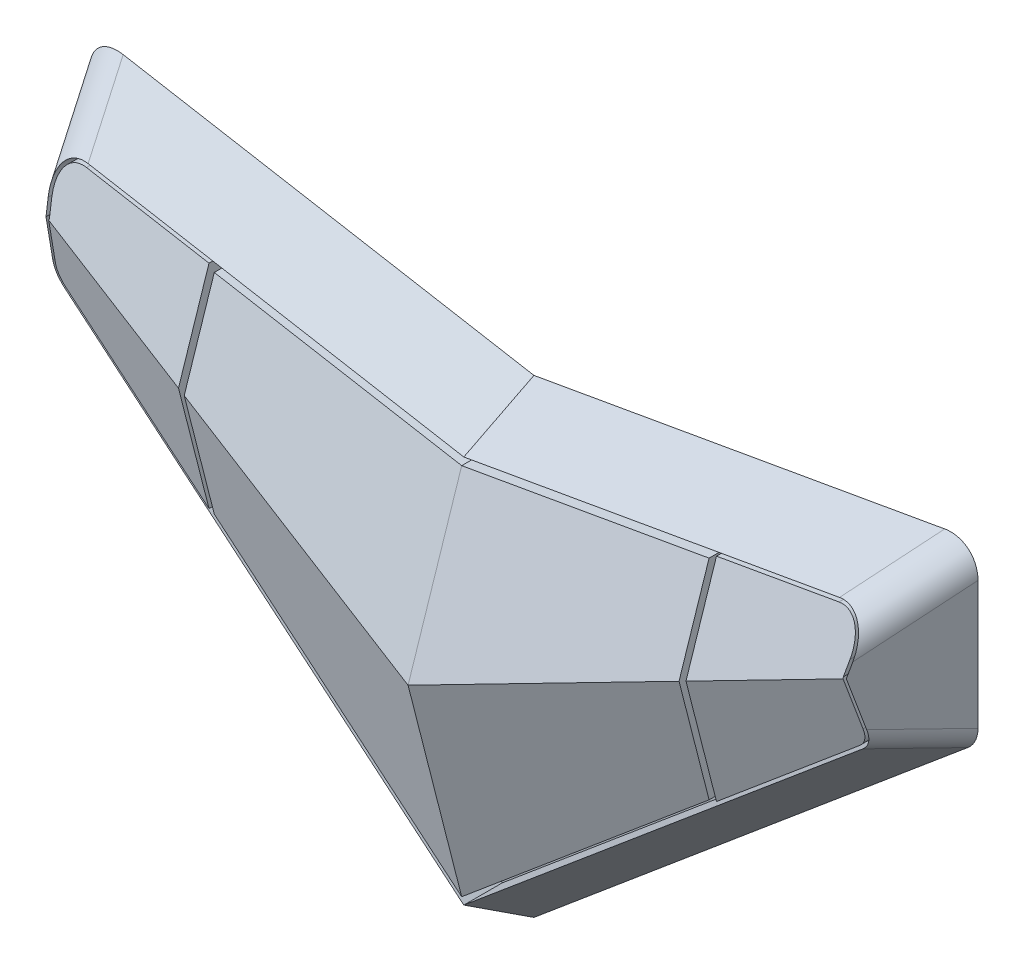
SolidWorks part; units mm, degrees
ref_plane "前视基准面" through (0, 0, 0) normal (0, 0, 1) x (1, 0, 0)
ref_plane "上视基准面" through (0, 0, 0) normal (0, 1, 0) x (1, 0, 0)
ref_plane "右视基准面" through (0, 0, 0) normal (1, 0, 0) x (0, 0, -1)
other "Configuration Table"
sketch "草图1" plane through (0, 0, 0) normal (0, 0, 1) x (1, 0, 0)
  line L0 (0, 79.8108) -> (0, -65.0792) construction
  line L1 (0, 74) -> (70, 86.3429)
  line L2 (70, 86.3429) -> (70, 58.737)
  line L3 (70, 58.737) -> (0, 0)
  line L4 (-70, 58.737) -> (0, 0)
  line L5 (-70, 86.3429) -> (-70, 58.737)
  line L6 (0, 74) -> (-70, 86.3429)
  point P5 (71.2745, 57.3374)
  point P8 (60, 66.0101)
  point P11 (70, 70)
  point P12 (70, 57.483)
  dimension "D1" = 70
  dimension "D2" = 130
  dimension "D3" = 74
  dimension "D4" = 100
ref_plane "基准面1" through (0, 0, 20) normal (0, 0, 1) x (1, 0, 0)
sketch "草图2" plane through (0, 0, 20) normal (0, 0, 1) x (1, 0, 0)
  line L12 (60, 74.4254) -> (0, 63.8457)
  line L13 (60, 63.4001) -> (60, 74.4254)
  line L14 (0, 13.0541) -> (60, 63.4001)
  line L15 (-60, 63.4001) -> (0, 13.0541)
  line L16 (-60, 74.4254) -> (-60, 63.4001)
  line L17 (0, 63.8457) -> (-60, 74.4254)
  line L18 (60, 74.4254) -> (0, 63.8457)
  line L19 (60, 63.4001) -> (60, 74.4254)
  line L20 (0, 13.0541) -> (60, 63.4001)
  line L21 (-60, 63.4001) -> (0, 13.0541)
  line L22 (-60, 74.4254) -> (-60, 63.4001)
  line L23 (0, 63.8457) -> (-60, 74.4254)
  dimension "D1" = 10
loft "放样1" add profiles "草图1", "草图2"
chamfer "倒角1" distance 10 angle 45 4 edges
fillet "圆角3" radius 5 4 edges
sketch "草图7" plane through (0, 0, 0) normal (0, 0, 1) x (1, 0, 0)
  line L0 (-40, 75.4399) -> (-40, 40.7801)
  line L1 (-59.2234, 78.8295) -> (0, 68.3869) construction
  line L2 (0, 7.2161) -> (-62.8746, 59.9742) construction
  line L3 (-40, 40.7801) -> (0, 7.2161)
  line L4 (0, 7.2161) -> (0, 41.623) construction
  line L5 (-40, 75.4399) -> (0, 68.3869)
  line L6 (40, 75.4399) -> (0, 68.3869)
  line L7 (40, 40.7801) -> (0, 7.2161)
  line L8 (40, 75.4399) -> (40, 40.7801)
  line L9 (-39, 74.2482) -> (0, 67.3714)
  line L10 (39, 74.2482) -> (0, 67.3714)
  line L11 (39, 74.2482) -> (39, 41.2464)
  line L12 (39, 41.2464) -> (0, 8.5215)
  line L13 (-39, 41.2464) -> (0, 8.5215)
  line L14 (-39, 74.2482) -> (-39, 41.2464)
  dimension "D1" = 40
  dimension "D2" = 1
extrude "切除-拉伸2" cut sketch "草图7" along normal through all from offset 5
sketch "草图9" plane through (0, 0, 0) normal (0, 0, 1) x (1, 0, 0)
  line L0 (-40, 75.4399) -> (0, 68.3869) construction
  line L1 (40, 75.4399) -> (0, 68.3869) construction
  line L2 (40, 75.4399) -> (59.2234, 78.8295) construction
  line L3 (63.4224, 73.1743) -> (63.0817, 71.0385) construction
  line L4 (63.0817, 71.0385) -> (64.1526, 63.549) construction
  line L5 (62.8746, 59.9742) -> (40, 40.7801) construction
  line L6 (0, 7.2161) -> (40, 40.7801) construction
  line L7 (-40, 40.7801) -> (0, 7.2161) construction
  line L8 (-40, 40.7801) -> (-62.8746, 59.9742) construction
  line L9 (-64.1526, 63.549) -> (-63.0817, 71.0385) construction
  line L10 (-63.0817, 71.0385) -> (-63.4224, 73.1743) construction
  line L11 (-59.2234, 78.8295) -> (-40, 75.4399) construction
  line L12 (-40, 75.4399) -> (0, 68.3869)
  line L13 (40, 75.4399) -> (0, 68.3869)
  line L14 (40, 75.4399) -> (59.2234, 78.8295)
  line L15 (63.4224, 73.1743) -> (63.0817, 71.0385)
  line L16 (63.0817, 71.0385) -> (64.1526, 63.549)
  line L17 (62.8746, 59.9742) -> (40, 40.7801)
  line L18 (0, 7.2161) -> (40, 40.7801)
  line L19 (-40, 40.7801) -> (0, 7.2161)
  line L20 (-40, 40.7801) -> (-62.8746, 59.9742)
  line L21 (-64.1526, 63.549) -> (-63.0817, 71.0385)
  line L22 (-63.0817, 71.0385) -> (-63.4224, 73.1743)
  line L23 (-59.2234, 78.8295) -> (-40, 75.4399)
  line L24 (-59.3102, 78.3371) -> (-40.0868, 74.9475)
  line L25 (-40.0868, 74.9475) -> (0, 67.8791)
  line L26 (40.0868, 74.9475) -> (0, 67.8791)
  line L27 (40.0868, 74.9475) -> (59.3102, 78.3371)
  line L28 (62.9286, 73.2531) -> (62.576, 71.0426)
  line L29 (62.576, 71.0426) -> (63.6577, 63.4783)
  line L30 (62.5532, 60.3572) -> (39.6786, 41.1631)
  line L31 (0, 7.8688) -> (39.6786, 41.1631)
  line L32 (-39.6786, 41.1631) -> (0, 7.8688)
  line L33 (-39.6786, 41.1631) -> (-62.5532, 60.3572)
  line L34 (-63.6577, 63.4783) -> (-62.576, 71.0426)
  line L35 (-62.576, 71.0426) -> (-62.9286, 73.2531)
  ellipse E0 centre (57.7639, 71.7605) end of major axis (53.8379, 65.0674) minor radius 4.8981 (63.4224, 73.1743) -> (59.2234, 78.8295) ccw construction
  ellipse E1 centre (57.7639, 64.4427) end of major axis (51.8576, 67.9829) minor radius 4.9757 (62.8746, 59.9742) -> (64.1526, 63.549) ccw construction
  ellipse E2 centre (-57.7639, 64.4427) end of major axis (-51.8576, 67.9829) minor radius 4.9757 (-64.1526, 63.549) -> (-62.8746, 59.9742) ccw construction
  ellipse E3 centre (-57.7639, 71.7605) end of major axis (-53.8379, 65.0674) minor radius 4.8981 (-59.2234, 78.8295) -> (-63.4224, 73.1743) ccw construction
  ellipse E4 centre (57.7639, 71.7605) end of major axis (53.8379, 65.0674) minor radius 4.8981 (63.4224, 73.1743) -> (59.2234, 78.8295) ccw
  ellipse E5 centre (57.7639, 64.4427) end of major axis (51.8576, 67.9829) minor radius 4.9757 (62.8746, 59.9742) -> (64.1526, 63.549) ccw
  ellipse E6 centre (-57.7639, 64.4427) end of major axis (-51.8576, 67.9829) minor radius 4.9757 (-64.1526, 63.549) -> (-62.8746, 59.9742) ccw
  ellipse E7 centre (-57.7639, 71.7605) end of major axis (-53.8379, 65.0674) minor radius 4.8981 (-59.2234, 78.8295) -> (-63.4224, 73.1743) ccw
  spline S0 degree 1 poles (62.9286, 73.2531) (59.3102, 78.3371) knots 0 0 1 1 construction
  spline S1 degree 1 poles (62.5532, 60.3572) (63.6577, 63.4783) knots 0 0 1 1 construction
  spline S2 degree 1 poles (-63.6577, 63.4783) (-62.5532, 60.3572) knots 0 0 1 1 construction
  spline S3 degree 1 poles (-59.3102, 78.3371) (-62.9286, 73.2531) knots 0 0 1 1 construction
  spline S4 degree 3 poles (59.3102, 78.3371) (59.606, 78.3893) (60.2361, 78.4277) (61.0232, 78.2581) (61.7076, 77.8882) (62.4586, 77.1307) (62.9425, 75.9586) (63.0646, 74.4897) (62.9925, 73.6532) (62.9286, 73.2531) knots 2.124821 2.124821 2.124821 2.124821 2.313531 2.50224 2.69095 2.879659 3.257079 3.445788 3.634498 3.634498 3.634498 3.634498
  spline S5 degree 3 poles (63.6577, 63.4783) (63.7012, 63.1738) (63.7219, 62.5362) (63.5357, 61.6989) (63.1568, 60.9587) (62.7681, 60.5375) (62.5532, 60.3572) knots 2.896914 2.896914 2.896914 2.896914 3.090732 3.28455 3.478368 3.672187 3.672187 3.672187 3.672187
  spline S6 degree 3 poles (-62.5532, 60.3572) (-62.7681, 60.5375) (-63.1568, 60.9587) (-63.5357, 61.6989) (-63.7219, 62.5362) (-63.7012, 63.1738) (-63.6577, 63.4783) knots 2.610999 2.610999 2.610999 2.610999 2.804817 2.998635 3.192453 3.386272 3.386272 3.386272 3.386272
  spline S7 degree 3 poles (-62.9286, 73.2531) (-62.9925, 73.6532) (-63.0646, 74.4897) (-62.9425, 75.9586) (-62.4586, 77.1307) (-61.7076, 77.8882) (-61.0232, 78.2581) (-60.2361, 78.4277) (-59.606, 78.3893) (-59.3102, 78.3371) knots 2.648688 2.648688 2.648688 2.648688 2.837397 3.026107 3.403526 3.592236 3.780945 3.969655 4.158364 4.158364 4.158364 4.158364
  dimension "D1" = 0.5
extrude "切除-拉伸3" cut sketch "草图9" along normal through all from offset 5
